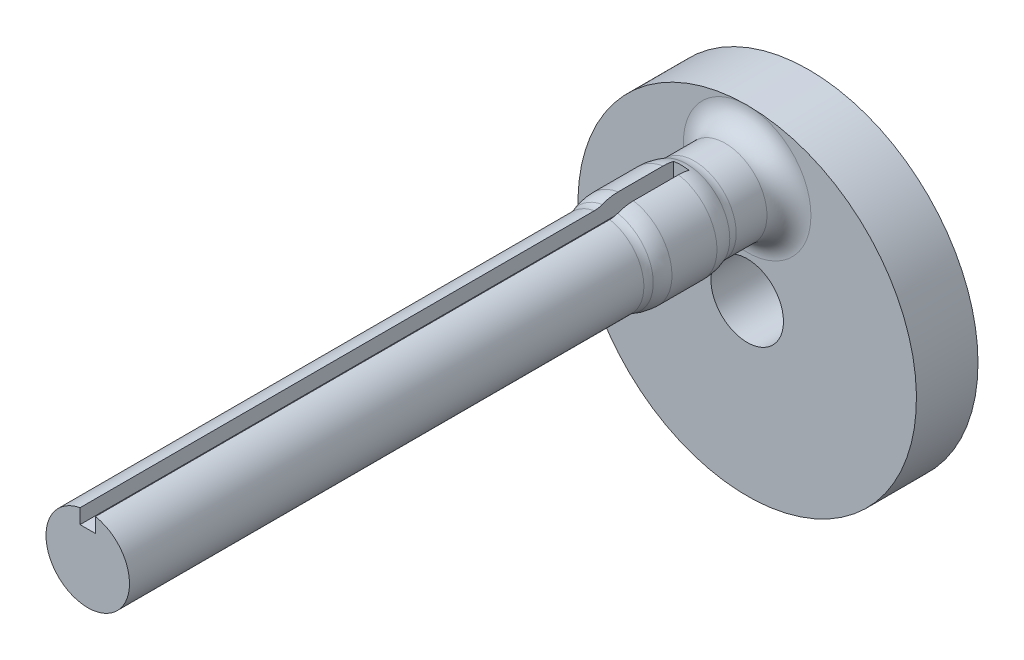
SolidWorks part; units mm, degrees
ref_plane "Plan de face" through (0, 0, 0) normal (0, 0, 1) x (1, 0, 0)
ref_plane "Plan de dessus" through (0, 0, 0) normal (0, 1, 0) x (1, 0, 0)
ref_plane "Plan de droite" through (0, 0, 0) normal (1, 0, 0) x (0, 0, -1)
sketch "Esquisse1" plane through (0, 0, 0) normal (0, 0, 1) x (1, 0, 0)
  circle A0 centre (0, 0) radius 7.7
  dimension "D1" = 15.4
extrude "Boss.-Extru.1" add sketch "Esquisse1" along normal blind 2.8
sketch "Esquisse2" plane through (0, 0, 2.8) normal (0, 0, 1) x (1, 0, 0)
  circle A0 centre (0, 4.8) radius 1.9
  point P2 (-0.5973, 5.0709)
  dimension "D2" = 3.8
  dimension "D1" = 4.8
extrude "Boss.-Extru.2" add sketch "Esquisse2" along normal blind 30
sketch "Esquisse3" plane through (0, 0, 2.8) normal (0, 0, 1) x (1, 0, 0)
  circle A0 centre (0, 0) radius 1.65
  dimension "D1" = 3.3
extrude "Enlèv. mat.-Extru.1" cut sketch "Esquisse3" against normal through all
fillet "Congé2" radius 1 1 edges at (1.9, 4.8, 2.8)
ref_plane "Plan1" through (0, 0, 3.8) normal (0, 0, 1) x (1, 0, 0)
ref_plane "Plan2" through (0, 0, 5.8) normal (0, 0, 1) x (1, 0, 0)
sketch "Esquisse4" plane through (0, 0, 5.8) normal (0, 0, 1) x (1, 0, 0)
  circle A2 centre (0, 4.8) radius 2.1
  circle A3 centre (0, 4.8) radius 2.1
  circle A4 centre (0, 4.8) radius 1.9
  circle A5 centre (0, 4.8) radius 1.9
  dimension "D1" = 0.2
  dimension "D2" = 0
extrude "Boss.-Extru.3" add sketch "Esquisse4" along normal blind 3
fillet "Congé3" radius 1 2 edges at (1.9, 4.8, 5.8) (1.9, 4.8, 8.8)
fillet "Congé4" radius 2 2 edges at (2.1, 4.8, 5.8) (2.1, 4.8, 8.8)
sketch "Esquisse5" plane through (0, 0, 5.8) normal (0, 0, 1) x (1, 0, 0)
  line L0 (-0.35, 7.4) -> (0.35, 6) construction
  line L1 (-0.35, 6) -> (0.35, 6)
  line L2 (-0.35, 6) -> (-0.35, 7.4)
  line L3 (-0.35, 7.4) -> (0.35, 7.4)
  line L4 (0.35, 6) -> (0.35, 7.4)
  circle A0 centre (0, 4.8) radius 1.9667 construction
  circle A1 centre (0, 4.8) radius 1.9
  circle A2 centre (0, 4.8) radius 1.9 construction
  point P4 (0, 6.7)
  dimension "D2" = 1.2
  dimension "D3" = 0.7
  dimension "D1" = 0
extrude "Enlèv. mat.-Extru.2" cut sketch "Esquisse5" along normal through all
